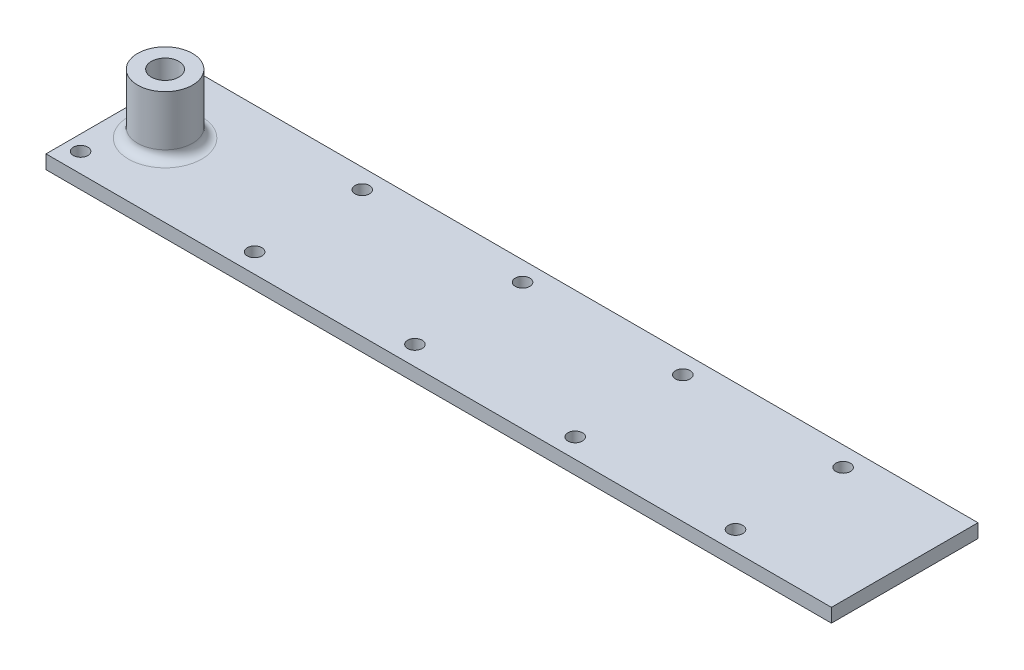
SolidWorks part; units mm, degrees
note: '?' marks a value the reader was unsure of.
ref_plane "Front Plane" through (0, 0, 0) normal (0, 0, 1) x (1, 0, 0)
ref_plane "Top Plane" through (0, 0, 0) normal (0, 1, 0) x (1, 0, 0)
ref_plane "Right Plane" through (0, 0, 0) normal (1, 0, 0) x (0, 0, -1)
sketch "Sketch1" plane through (0, 0, 0) normal (0, 1, 0) x (1, 0, 0)
  circle A0 centre (0, 0) radius 3
  circle A1 centre (0, 0) radius 6
  dimension "D1" = 6
  dimension "D2" = 12
extrude "Boss-Extrude1" add sketch "Sketch1" against normal blind 13
sketch "Sketch2" plane through (0, -13, 0) normal (0, -1, 0) x (1, 0, 0)
  line L0 (-7.5, 0) -> (161.5, 0) construction
  line L1 (-10, 16) -> (161.5, 16)
  line L3 (-10, -16) -> (161.5, -16)
  line L4 (161.5, 16) -> (161.5, -16)
  line L5 (-1.5, 7.5) -> (-1.5, -7.5) construction
  line L6 (-1.5, -7.5) -> (1.5, -7.5) construction
  line L7 (1.5, -7.5) -> (1.5, 7.5) construction
  line L8 (1.5, 7.5) -> (-1.5, 7.5) construction
  line L9 (136.3, -11.75) -> (109.2211, -11.75) construction
  line L10 (136.3, 11.75) -> (109.2211, 11.75) construction
  line L11 (31.3, 11.75) -> (8.143, 11.75) construction
  line L12 (31.3, -11.75) -> (8.143, -11.75) construction
  line L14 (-10, 16) -> (-10, -16)
  circle A0 centre (0, 0) radius 6 construction
  circle A2 centre (0, 0) radius 3 construction
  circle A3 centre (136.3, -11.75) radius 1.5875
  circle A4 centre (136.3, 11.75) radius 1.5875
  circle A5 centre (101.3, -11.75) radius 1.5875
  circle A6 centre (66.3, -11.75) radius 1.5875
  circle A7 centre (31.3, -11.75) radius 1.5875
  circle A8 centre (101.3, 11.75) radius 1.5875
  circle A9 centre (66.3, 11.75) radius 1.5875
  circle A10 centre (31.3, 11.75) radius 1.5875
  circle A11 centre (-6.7, 11.75) radius 1.5875
  circle A12 centre (-6.7, -11.75) radius 1.5875
  point P10 (-6, 0)
  point P14 (1.5, 0)
  point P17 (3, 0)
  point P18 (-3, 0)
  point P45 (-7.5, 0)
  dimension "D7" = 3.175
  dimension "D8" = 25.2
  dimension "D9" = 4.25
  dimension "D12" = 3.175
  dimension "D13" = 38
  dimension "D14" = 10
  dimension "D2" = 32
  dimension "D3" = 163
  dimension "D4" = 3
  dimension "D5" = 15
  dimension "D6" = 1.5
  dimension "D15" = 6
  dimension "D10" = 4
  dimension "D11" = 4
extrude "Boss-Extrude2" add sketch "Sketch2" along normal blind 3 separate body
ref_point "Point2"
ref_axis "Axis4" through (0, 0, 0) along (0, 0, 1)?
ref_plane "Plane2" through (0, 0, 0) normal (-1, 0, 0) x (0, 0, 1)
sketch "Sketch7" plane through (0, 0, 0) normal (-1, 0, 0) x (0, 0, 1)
  line L0 (-16, -13) -> (16, -13) construction
  line L1 (-6, -13) -> (6, -13) construction
  line L2 (0, -16) -> (0, 0) construction
  line L3 (-16, -16) -> (16, -16) construction
  line L4 (-4.5661, -13.348) -> (-5.9339, -13.652)
  line L5 (4.5661, -13.348) -> (5.9339, -13.652)
  line L6 (-7.5, -15.6043) -> (-7.5, -16)
  line L7 (7.5, -15.6043) -> (7.5, -16)
  line L8 (-3, -11.3957) -> (-3, 0)
  line L9 (6, 0) -> (-6, 0) construction
  line L10 (3, 0) -> (-3, 0) construction
  line L11 (3, -11.3957) -> (3, 0)
  line L12 (-3, 0) -> (-6, 0)
  line L13 (3, 0) -> (6, 0)
  line L14 (-6, 0) -> (-6, -13)
  line L15 (6, 0) -> (6, -13)
  line L16 (-6, -13) -> (-16, -13)
  line L17 (6, -13) -> (16, -13)
  line L18 (-16, -13) -> (-16, -16)
  line L19 (16, -13) -> (16, -16)
  line L22 (-7.5, -16) -> (7.5, -16)
  line L23 (-3, 0) -> (3, 0)
  line L24 (-3, -11.3957) -> (3, -11.3957)
  arc A0 (-5.9339, -13.652) -> (-7.5, -15.6043) centre (-5.5, -15.6043) ccw
  arc A1 (-3, -11.3957) -> (-4.5661, -13.348) centre (-5, -11.3957) cw
  arc A2 (4.5661, -13.348) -> (3, -11.3957) centre (5, -11.3957) cw
  arc A3 (7.5, -15.6043) -> (5.9339, -13.652) centre (5.5, -15.6043) ccw
  point P0 (-3, -13)
  point P1 (3, -13)
  point P35 (-7.5, -14)
  point P38 (-3, -13)
  point P41 (3, -13)
  point P44 (7.5, -14)
  dimension "D3" = 2
  dimension "D4" = 2
  dimension "D5" = 2
  dimension "D6" = 2
  dimension "D1" = 15
  dimension "D2" = 2
extrude "Cut-Extrude1" cut sketch "Sketch7" against normal mid plane 3 contours L22 L2 L24 A1 L4 A0 L6 | L2 L22 L7 A3 L5 A2 L24
sketch "Sketch8" plane through (0, 0, 0) normal (-1, 0, 0) x (0, 0, 1)
  line L1 (16, -13) -> (-16, -13) construction
  line L3 (-8, -13) -> (-6, -13)
  line L4 (-6, -13) -> (-6, -11)
  line L5 (0, 4.0956) -> (0, -21.1532) construction
  line L7 (-6.5858, -12.4142) -> (-8, -11) construction
  line L8 (-6, -11) -> (-8, -11) construction
  line L9 (-8, -11) -> (-8, -13) construction
  arc A0 (-8, -13) -> (-6, -11) centre (-8, -11) ccw
ref_axis "Axis5" through (0, -13, 0) along (0, 1, 0)?
revolve "Revolve1" add sketch "Sketch8" angle 360 about L5
